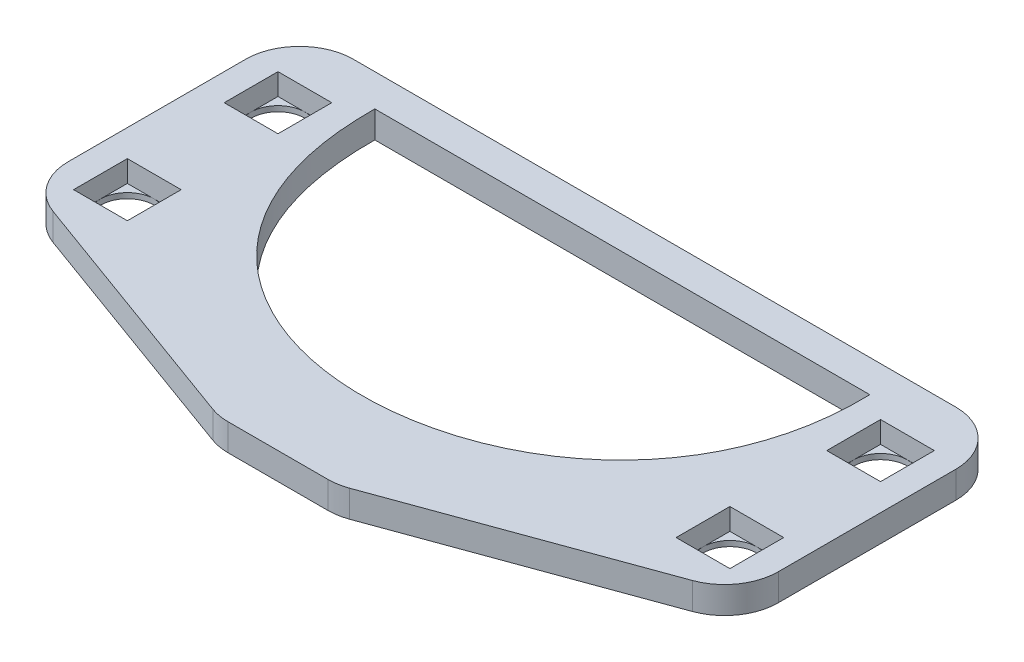
SolidWorks part; units mm, degrees
ref_plane "Front Plane" through (0, 0, 0) normal (0, 0, 1) x (1, 0, 0)
ref_plane "Top Plane" through (0, 0, 0) normal (0, 1, 0) x (1, 0, 0)
ref_plane "Right Plane" through (0, 0, 0) normal (1, 0, 0) x (0, 0, -1)
sketch "Sketch1" plane through (0, 0, 0) normal (0, 1, 0) x (1, 0, 0)
  line L1 (0, 0) -> (66, 0)
  line L2 (0, 0) -> (0, 35)
  line L3 (0, 35) -> (66, 35)
  line L4 (66, 0) -> (66, 35)
  dimension "D1" = 66
  dimension "D2" = 35
extrude "Boss-Extrude1" add sketch "Sketch1" along normal blind 2.5
sketch "Sketch2" plane through (0, 2.5, 0) normal (0, 1, 0) x (1, 0, 0)
  line L0 (10, 32) -> (56, 32)
  line L1 (0, 35) -> (0, 0) construction
  line L2 (66, 35) -> (0, 35) construction
  line L3 (66, 0) -> (66, 35) construction
  line L5 (7.5, 30.5) -> (2.5, 30.5)
  line L6 (7.5, 30.5) -> (7.5, 25.5)
  line L7 (7.5, 25.5) -> (2.5, 25.5)
  line L8 (2.5, 30.5) -> (2.5, 25.5)
  line L9 (7.5, 30.5) -> (2.5, 25.5) construction
  line L10 (7.5, 25.5) -> (2.5, 30.5) construction
  line L11 (7.5, 16.5) -> (2.5, 16.5)
  line L12 (7.5, 16.5) -> (7.5, 11.5)
  line L13 (7.5, 11.5) -> (2.5, 11.5)
  line L14 (2.5, 16.5) -> (2.5, 11.5)
  line L15 (7.5, 16.5) -> (2.5, 11.5) construction
  line L16 (7.5, 11.5) -> (2.5, 16.5) construction
  line L17 (58.5, 16.5) -> (63.5, 16.5)
  line L18 (58.5, 16.5) -> (58.5, 11.5)
  line L19 (58.5, 11.5) -> (63.5, 11.5)
  line L20 (63.5, 16.5) -> (63.5, 11.5)
  line L21 (58.5, 16.5) -> (63.5, 11.5) construction
  line L22 (58.5, 11.5) -> (63.5, 16.5) construction
  line L23 (58.5, 30.5) -> (63.5, 30.5)
  line L24 (58.5, 30.5) -> (58.5, 25.5)
  line L25 (58.5, 25.5) -> (63.5, 25.5)
  line L26 (63.5, 30.5) -> (63.5, 25.5)
  line L27 (58.5, 30.5) -> (63.5, 25.5) construction
  line L28 (58.5, 25.5) -> (63.5, 30.5) construction
  circle A0 centre (5, 28) radius 2.5
  circle A1 centre (5, 14) radius 2.5
  circle A2 centre (61, 28) radius 2.5
  circle A3 centre (61, 14) radius 2.5
  spline S0 degree 3 poles (56, 32) (56.8358, 1.6689) (9.6214, -0.7676) (10, 32) knots 0 0 0 0 1 1 1 1
  dimension "D3" = 3
  dimension "D5" = 5
  dimension "D6" = 5
  dimension "D7" = 5
  dimension "D8" = 5
  dimension "D1" = 46
  dimension "D2" = 10
  dimension "D4" = 14
  dimension "D9" = 5
  dimension "D10" = 5
  dimension "D11" = 7
  dimension "D12" = 5
  dimension "D13" = 5
  dimension "D14" = 5
  dimension "D15" = 5
  dimension "D16" = 5
  dimension "D17" = 5
  dimension "D18" = 5
  dimension "D19" = 5
extrude "Cut-Extrude1" cut sketch "Sketch2" against normal through all contours A0 | A0 | A1 | A3 | A2 | S0 L0 region at (5, 2.5, -28)
extrude "Cut-Extrude2" cut sketch "Sketch2<3>" against normal blind 2 contours A1 L13 L12 | A1 L12 L11 | A1 L11 L14 | A1 L14 L13 | A0 L5 L8 | A0 L6 L5 | A0 L7 L6 | A0 L8 L7 | A2 L23 L24 | A2 L26 L23 | A2 L25 L26 | A2 L24 L25 | A3 L19 L20 | A3 L18 L19 | A3 L17 L18 | A3 L20 L17 region at (6.9416, 2.5, -29.9416) region at (3.0584, 2.5, -29.9416) region at (6.9416, 2.5, -26.0584) region at (3.0584, 2.5, -26.0584) region at (6.9416, 2.5, -15.9416) region at (3.0584, 2.5, -15.9416) region at (6.9416, 2.5, -12.0584) region at (3.0584, 2.5, -12.0584) region at (59.0584, 2.5, -15.9416) region at (62.9416, 2.5, -15.9416) region at (59.0584, 2.5, -12.0584) region at (62.9416, 2.5, -12.0584) region at (59.0584, 2.5, -29.9416) region at (62.9416, 2.5, -29.9416) region at (59.0584, 2.5, -26.0584) region at (62.9416, 2.5, -26.0584)
sketch "Sketch2<3>" plane through (0, 2.5, 0) normal (0, 1, 0) x (1, 0, 0) same geometry as "Sketch2"
chamfer "Chamfer1" distance 10 angle 70 2 edges at (66, 1.25, 0) (0, 1.25, 0) first distance on face at (66, 1.25, -17.5) first distance on face at (0, 1.25, -17.5)
fillet "Fillet1" radius 5 6 edges at (27.4748, 1.25, 0) (38.5252, 1.25, 0) (66, 1.25, -10) (66, 1.25, -35) (0, 1.25, -35) (0, 1.25, -10)
